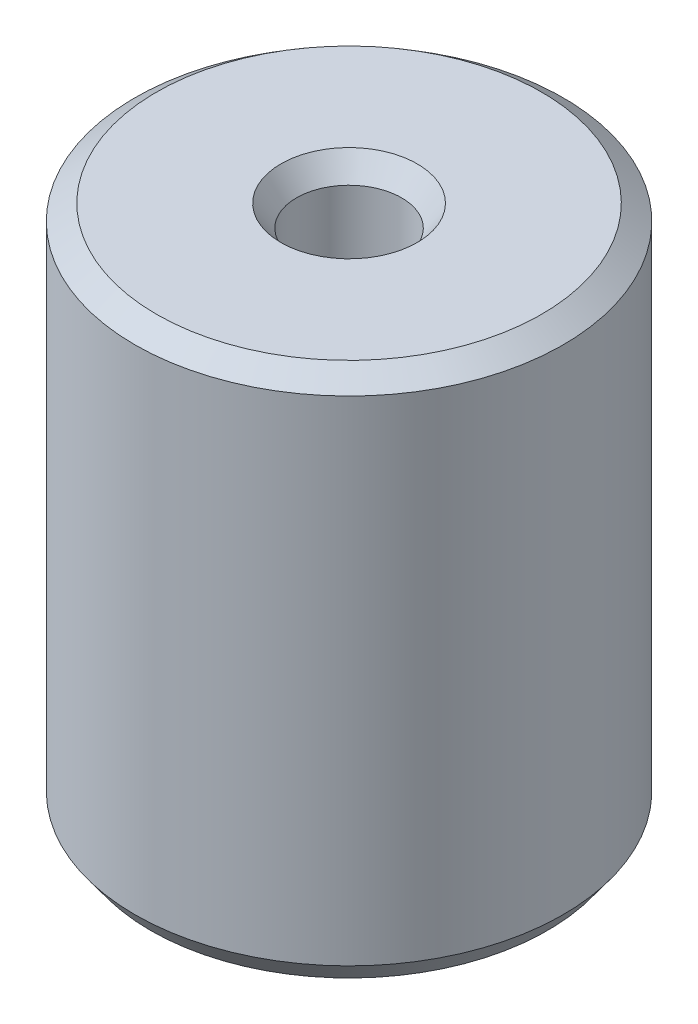
SolidWorks part; units mm, degrees
ref_plane "Front Plane" through (0, 0, 0) normal (0, 0, 1) x (1, 0, 0)
ref_plane "Top Plane" through (0, 0, 0) normal (0, 1, 0) x (1, 0, 0)
ref_plane "Right Plane" through (0, 0, 0) normal (1, 0, 0) x (0, 0, -1)
sketch "Sketch1" plane through (0, 0, 0) normal (0, 1, 0) x (1, 0, 0)
  circle A0 centre (0, 0) radius 5
  dimension "SLEEVE_OD" = 10
extrude "Boss-Extrude1" add sketch "Sketch1" along normal blind 12.3946
sketch "Sketch2" plane through (0, 0, 0) normal (0, 1, 0) x (1, 0, 0)
  circle A0 centre (0, 0) radius 1.2268
  dimension "BORE_D" = 2.4535
extrude "Cut-Extrude1" cut sketch "Sketch2" along normal through all
chamfer "Chamfer1" distance 0.3657 angle 54.024 4 edges at (0, 12.3946, 1.2268) (0, 0, 1.2268) (0, 0, 5) (0, 12.3946, 5) first distance on face at (0, 12.3946, 1.2268) first distance on face at (0, 0, 1.2268) first distance on face at (0, 12.3946, 5)
